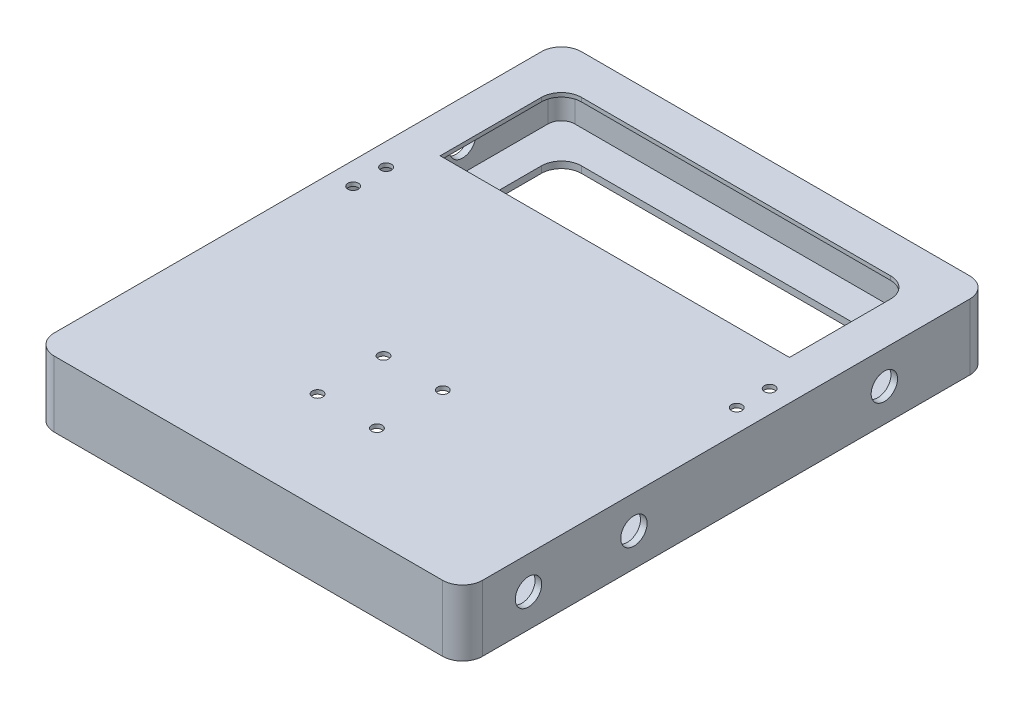
SolidWorks part; units mm, degrees
material "PPE"
ref_plane "Front Plane" through (0, 0, 0) normal (0, 0, 1) x (1, 0, 0)
ref_plane "Top Plane" through (0, 0, 0) normal (0, 1, 0) x (1, 0, 0)
ref_plane "Right Plane" through (0, 0, 0) normal (1, 0, 0) x (0, 0, -1)
sketch "Sketch1" plane through (0, 0, 0) normal (0, 1, 0) x (1, 0, 0)
  line L1 (-147.3016, -200) -> (147.3016, -200)
  line L2 (-162.5, -184.8016) -> (-162.5, 184.8016)
  line L3 (-147.3016, 200) -> (147.3016, 200)
  line L4 (162.5, -184.8016) -> (162.5, 184.8016)
  line L5 (-162.5, -200) -> (162.5, 200) construction
  line L6 (-162.5, 200) -> (162.5, -200) construction
  arc A0 (-147.3016, -200) -> (-162.5, -184.8016) centre (-147.3016, -184.8016) cw
  arc A1 (147.3016, -200) -> (162.5, -184.8016) centre (147.3016, -184.8016) ccw
  arc A2 (147.3016, 200) -> (162.5, 184.8016) centre (147.3016, 184.8016) cw
  arc A3 (-162.5, 184.8016) -> (-147.3016, 200) centre (-147.3016, 184.8016) cw
  point P0 (0, 0)
  dimension "D3" = 15.1984
  dimension "D1" = 325
  dimension "D2" = 400
extrude "Boss-Extrude1" add sketch "Sketch1" along normal blind 50
shell "Shell1" thickness 5 removed face at (0, 50, 0)
sketch "Sketch2" plane through (162.5, 0, 0) normal (1, 0, 0) x (0, 0, -1)
  line L0 (-200, 50) -> (-200, 0) construction
  line L2 (200, 50) -> (200, 0) construction
  circle A0 centre (-150, 25) radius 10
  circle A1 centre (120, 25) radius 10
  circle A2 centre (-70, 25) radius 10
  point P8 (0, 0)
  point P9 (-200, 25)
  point P12 (-97.3076, 25)
  point P13 (0, 0)
  point P14 (0, 0)
  point P15 (-62.3063, 18.612)
  point P16 (0, 0)
  dimension "D2" = 20
  dimension "D3" = 20
  dimension "D5" = 20
  dimension "D1" = 50
  dimension "D4" = 80
  dimension "D6" = 130
extrude "Cut-Extrude1" cut sketch "Sketch2" against normal up to surface (325 mm away) up to face at (-162.5, 25, 0)
sketch "Sketch3" plane through (0, 50, 0) normal (0, 1, 0) x (1, 0, 0)
  line L0 (147.3016, 195) -> (-147.3016, 195) construction
  line L1 (157.5, -184.8016) -> (157.5, 184.8016) construction
  line L2 (-147.3016, -195) -> (147.3016, -195) construction
  line L3 (-157.5, 184.8016) -> (-157.5, -184.8016) construction
  line L4 (147.3016, 195) -> (-147.3016, 195)
  line L5 (157.5, -184.8016) -> (157.5, 184.8016)
  line L6 (-147.3016, -195) -> (147.3016, -195)
  line L7 (-157.5, 184.8016) -> (-157.5, -184.8016)
  arc A0 (-147.3016, 195) -> (-157.5, 184.8016) centre (-147.3016, 184.8016) ccw construction
  arc A1 (157.5, 184.8016) -> (147.3016, 195) centre (147.3016, 184.8016) ccw construction
  arc A2 (147.3016, -195) -> (157.5, -184.8016) centre (147.3016, -184.8016) ccw construction
  arc A3 (-157.5, -184.8016) -> (-147.3016, -195) centre (-147.3016, -184.8016) ccw construction
  arc A4 (-147.3016, 195) -> (-157.5, 184.8016) centre (-147.3016, 184.8016) ccw
  arc A5 (157.5, 184.8016) -> (147.3016, 195) centre (147.3016, 184.8016) ccw
  arc A6 (147.3016, -195) -> (157.5, -184.8016) centre (147.3016, -184.8016) ccw
  arc A7 (-157.5, -184.8016) -> (-147.3016, -195) centre (-147.3016, -184.8016) ccw
extrude "Boss-Extrude2" add sketch "Sketch3" against normal blind 3
sketch "Sketch4" plane through (0, 50, 0) normal (0, 1, 0) x (1, 0, 0)
  line L44 (-132.5, -170) -> (132.5, -170)
  line L45 (132.5, -170) -> (132.5, 170)
  line L46 (132.5, 170) -> (-132.5, 170)
  line L47 (-132.5, 170) -> (-132.5, -170)
  line L48 (-117.3016, -170) -> (117.3016, -170)
  line L49 (132.5, -154.8016) -> (132.5, 154.8016)
  line L50 (117.3016, 170) -> (-117.3016, 170)
  line L51 (-132.5, 154.8016) -> (-132.5, -154.8016)
  arc A32 (117.3016, -170) -> (132.5, -154.8016) centre (117.3016, -154.8016) ccw
  arc A33 (132.5, 154.8016) -> (117.3016, 170) centre (117.3016, 154.8016) ccw
  arc A34 (-117.3016, 170) -> (-132.5, 154.8016) centre (-117.3016, 154.8016) ccw
  arc A35 (-117.3016, -170) -> (-132.5, -154.8016) centre (-117.3016, -154.8016) cw
  dimension "D2" = 15.1984
  dimension "D1" = 30
extrude "Cut-Extrude2" cut sketch "Sketch4" against normal up to surface (50 mm away) up to face at (0, 0, 0)
sketch "Sketch6" plane through (0, 5, 0) normal (0, 1, 0) x (1, 0, 0)
  line L0 (147.3016, 200) -> (-147.3016, 200) construction
  line L1 (0, 0) -> (0, 132.8131) construction
  line L2 (-157.5, 184.8016) -> (-157.5, -184.8016) construction
  circle A0 centre (-145.5, 50) radius 4
  circle A1 centre (-145.5, 25) radius 4
  circle A2 centre (145.5, 25) radius 4
  circle A3 centre (145.5, 50) radius 4
  dimension "D3" = 8
  dimension "D4" = 8
  dimension "D1" = 25
  dimension "D2" = 150
  dimension "D5" = 12
extrude "Cut-Extrude3" cut sketch "Sketch6" against normal through all and the other way through all
sketch "Sketch7" plane through (0, 0, 0) normal (0, 0, 1) x (1, 0, 0)
  line L0 (-132.5, 50) -> (132.5, 50)
  line L1 (132.5, 50) -> (132.5, 47)
  line L2 (147.3016, 47) -> (-147.3016, 47) construction
  line L3 (132.5, 47) -> (-132.5, 47)
  line L4 (-132.5, 47) -> (-117.3016, 47) construction
  line L5 (-132.5, 47) -> (-132.5, 50)
extrude "Boss-Extrude4" add sketch "Sketch7" along normal blind 187
sketch "Sketch8" plane through (0, 50, 0) normal (0, 1, 0) x (1, 0, 0)
  line L0 (0, -3.599) -> (0, 78.9004) construction
  line L2 (-147.3016, -200) -> (147.3016, -200) construction
  circle A0 centre (-22.5, -125) radius 4
  circle A1 centre (-22.5, -75) radius 4
  circle A2 centre (22.5, -125) radius 4
  circle A3 centre (22.5, -75) radius 4
  point P11 (20, -126.1085)
  dimension "D3" = 8
  dimension "D1" = 50
  dimension "D2" = 22.5
  dimension "D4" = 75
extrude "Cut-Extrude4" cut sketch "Sketch8" against normal up to surface (3 mm away) up to face at (0, 47, -109.3164)
extrude "Boss-Extrude5" add sketch "Sketch7<2>" against normal blind 78
sketch "Sketch7<2>" plane through (0, 0, 0) normal (0, 0, 1) x (1, 0, 0) same geometry as "Sketch7"
